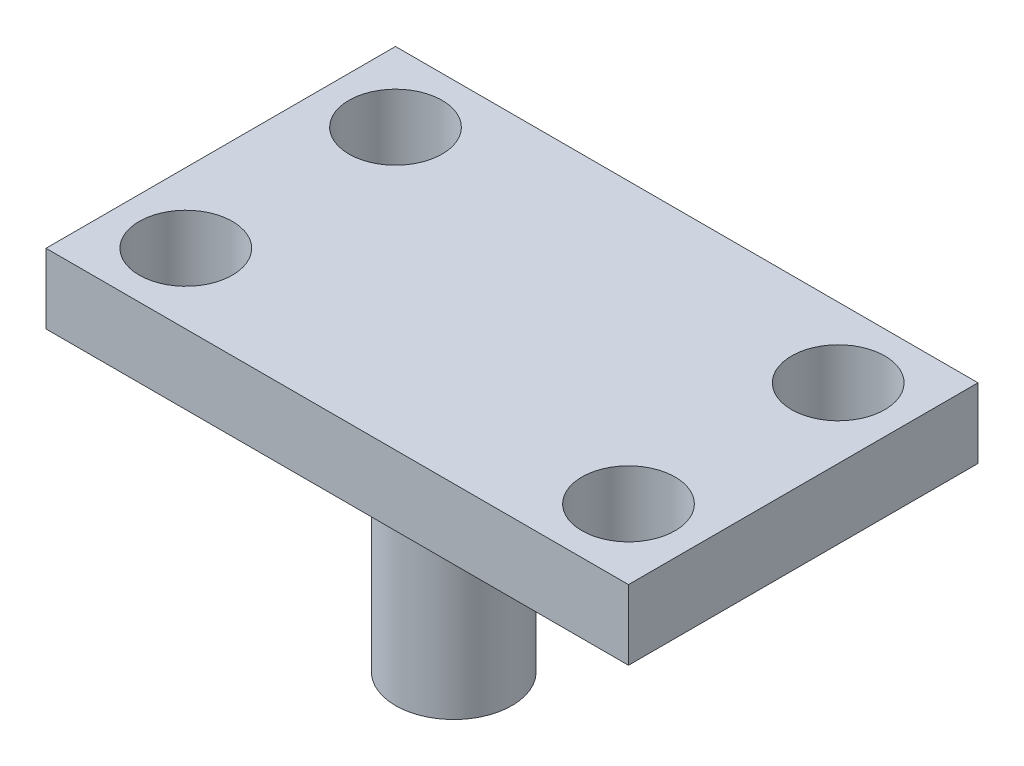
SolidWorks part; units mm, degrees
ref_plane "Front Plane" through (0, 0, 0) normal (0, 0, 1) x (1, 0, 0)
ref_plane "Top Plane" through (0, 0, 0) normal (0, 1, 0) x (1, 0, 0)
ref_plane "Right Plane" through (0, 0, 0) normal (1, 0, 0) x (0, 0, -1)
sketch "Sketch1" plane through (0, 0, 0) normal (0, 1, 0) x (1, 0, 0)
  line L1 (-125, 75) -> (125, 75)
  line L2 (-125, 75) -> (-125, -75)
  line L3 (-125, -75) -> (125, -75)
  line L4 (125, 75) -> (125, -75)
  line L5 (-125, 75) -> (125, -75) construction
  line L6 (-125, -75) -> (125, 75) construction
  circle A0 centre (0, -25) radius 25
  circle A1 centre (-95, -45) radius 20
  circle A2 centre (-95, 45) radius 20
  circle A3 centre (95, 45) radius 20
  circle A4 centre (95, -45) radius 20
  point P0 (0, 0)
  point P16 (0, 0)
  point P17 (0, 0)
  point P18 (0, 0)
  point P19 (0, 0)
  point P20 (0, 0)
  point P21 (85.833, -51.4998)
  point P22 (0, 0)
  point P23 (0, 0)
  point P24 (0, 0)
  dimension "D4" = 50
  dimension "D5" = 40
  dimension "D1" = 250
  dimension "D2" = 150
  dimension "D3" = 50
  dimension "D6" = 190
  dimension "D7" = 30
  dimension "D8" = 30
  dimension "D9" = 30
extrude "Boss-Extrude1" add sketch "Sketch1" along normal blind 30
extrude "Boss-Extrude2" add sketch "Sketch1<3>" along normal through all contours A0
sketch "Sketch1<3>" plane through (0, 0, 0) normal (0, 1, 0) x (1, 0, 0) same geometry as "Sketch1"
extrude "Boss-Extrude3" add sketch "Sketch1<4>" against normal blind 90 contours A0
sketch "Sketch1<4>" plane through (0, 0, 0) normal (0, 1, 0) x (1, 0, 0) same geometry as "Sketch1"
